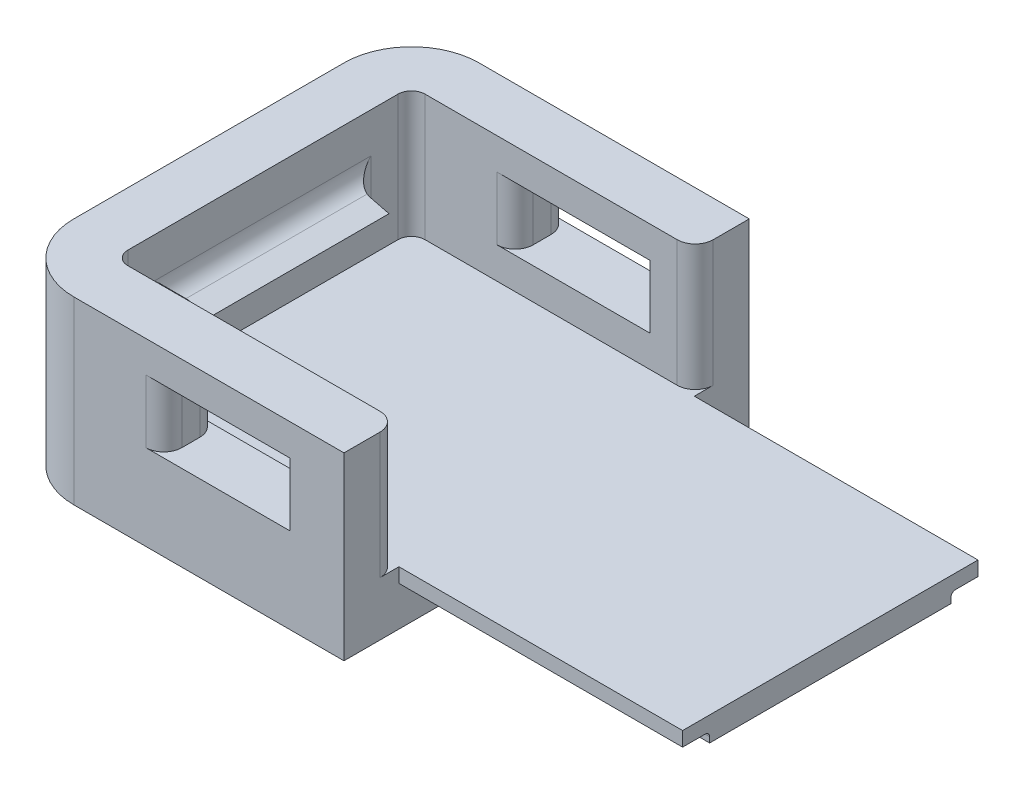
SolidWorks part; units mm, degrees
ref_plane "Alzado" through (0, 0, 0) normal (0, 0, 1) x (1, 0, 0)
ref_plane "Planta" through (0, 0, 0) normal (0, 1, 0) x (1, 0, 0)
ref_plane "Vista lateral" through (0, 0, 0) normal (1, 0, 0) x (0, 0, -1)
sketch "Croquis1" plane through (0, 0, 0) normal (0, 1, 0) x (1, 0, 0)
  line L0 (18.75, 0) -> (-18.75, 0) construction
  line L1 (15, 11.25) -> (-15, 11.25)
  line L2 (15, -11.25) -> (-15, -11.25)
  line L3 (-18.75, 7.5) -> (-18.75, -7.5)
  line L4 (18.75, 7.5) -> (18.75, -7.5)
  line L5 (0, -11.25) -> (0, 11.25) construction
  arc A0 (18.75, -7.5) -> (15, -11.25) centre (15, -7.5) cw
  arc A1 (-15, -11.25) -> (-18.75, -7.5) centre (-15, -7.5) cw
  arc A2 (18.75, 7.5) -> (15, 11.25) centre (15, 7.5) ccw
  arc A3 (-15, 11.25) -> (-18.75, 7.5) centre (-15, 7.5) ccw
  point P3 (0, 0)
  point P18 (0, 0)
  dimension "D1" = 3.75
  dimension "D2" = 37.5
  dimension "D3" = 22.5
  dimension "D4" = 7.5
extrude "Saliente-Extruir1" add sketch "Croquis1" along normal blind 3
sketch "Croquis2" plane through (0, 0, 0) normal (0, -1, 0) x (1, 0, 0)
  line L0 (15, -11.25) -> (-15, -11.25) construction
  circle A1 centre (0, 0) radius 7.63
  point P3 (0, -11.25)
  dimension "D1" = 15.26
extrude "Saliente-Extruir2" add sketch "Croquis2" along normal blind 3
sketch "Croquis3" plane through (0, 0, 0) normal (0, 0, 1) x (1, 0, 0)
  line L0 (7.63, -1.0671) -> (7.63, -3)
  line L1 (7.73, -1) -> (7.73, -3) construction
  line L2 (7.63, -1.0671) -> (9.73, -1.9262)
  line L3 (7.73, -1) -> (9.93, -1.9) construction
  line L4 (0, -3) -> (7.73, -3) construction
  line L5 (9.93, -1.9) -> (9.93, -3) construction
  line L6 (9.93, -3) -> (7.73, -3) construction
  line L7 (9.73, -3) -> (9.73, -1.9262) construction
  line L8 (7.73, -1.108) -> (9.73, -1.9262) construction
  line L9 (9.73, -1.9262) -> (9.73, -3)
  line L11 (7.73, -1.108) -> (7.73, -3) construction
  line L12 (-7.63, -3) -> (7.63, -3) construction
  line L13 (0, -3) -> (0, 0) construction
  line L14 (7.63, -3) -> (7.63, 0) construction
  line L15 (7.63, -3) -> (9.73, -3)
  dimension "D1" = 2.2
  dimension "D2" = 1.1
  dimension "D3" = 0.2
  dimension "D4" = 0.1
  dimension "D5" = 7.73
  dimension "D6" = 112.249
revolve "Revolución1" add sketch "Croquis3" angle 45 about L13 other way angle 15
sketch "Croquis5" plane through (0, 0, 0) normal (0, 0, 1) x (1, 0, 0)
  line L1 (-7.63, -3) -> (7.37, -3) construction
  line L3 (7.63, -1.0671) -> (7.63, -3) construction
  line L11 (7.73, -1) -> (7.73, -3) construction
  line L12 (-9.73, -1.9262) -> (-9.73, -3)
  line L13 (7.63, -1.0671) -> (9.73, -1.9262) construction
  line L18 (-7.63, -3) -> (-9.73, -3)
  line L19 (7.73, -1) -> (9.93, -1.9) construction
  line L20 (0, -3) -> (7.73, -3) construction
  line L25 (9.93, -1.9) -> (9.93, -3) construction
  line L26 (9.93, -3) -> (7.73, -3) construction
  line L27 (9.73, -3) -> (9.73, -1.9262) construction
  line L28 (7.73, -1.108) -> (9.73, -1.9262) construction
  line L29 (9.73, -1.9262) -> (9.73, -3) construction
  line L30 (7.73, -1.108) -> (7.73, -3) construction
  line L31 (0, -3) -> (0, 0) construction
  line L32 (7.63, -3) -> (9.73, -3) construction
  line L33 (-7.63, -1.0671) -> (-7.63, -3)
  line L34 (-7.63, -1.0671) -> (-9.73, -1.9262)
  dimension "D1" = 2.2
  dimension "D2" = 1.1
  dimension "D3" = 0.2
  dimension "D4" = 112.249
  dimension "D5" = 7.73
  dimension "D6" = 0.1
  dimension "D7" = 1.9329
revolve "Revolución2" add sketch "Croquis5" angle 45 about L31 other way angle 15
sketch "Croquis6" plane through (0, -3, 0) normal (0, -1, 0) x (1, 0, 0)
  line L0 (0, 0) -> (9.5627, -2.5623) construction
  line L1 (0, 0) -> (-9.5627, 2.5623) construction
  circle A2 centre (-9.5627, 2.5623) radius 1
  circle A3 centre (9.5627, -2.5623) radius 1
  dimension "D1" = 2
  dimension "D2" = 15
  dimension "D3" = 9.9
extrude "Cortar-Extruir1" cut sketch "Croquis6" against normal up to next
fillet "Redondeo4" radius 1 14 edges at (9.3985, -2.4631, 2.5183) (9.0986, -2.4631, -3.4481) (9.6036, -2.4631, -1.5631) (6.8801, -2.4631, -6.8801) (5.3952, -2.0336, -5.3952) (7.37, -2.0336, 1.9748) (-7.37, -2.0336, -1.9748) (-9.3985, -2.4631, -2.5183) (-9.6036, -2.4631, 1.5631) (-9.0986, -2.4631, 3.4481) (-5.3952, -2.0336, 5.3952) (-6.8801, -2.4631, 6.8801) (-7.37, -1.0671, 1.9748) (7.37, -1.0671, -1.9748)
sketch "Croquis8" plane through (0, 3, 0) normal (0, 1, 0) x (1, 0, 0)
  line L0 (15, 8.25) -> (-15, 8.25)
  line L1 (-15.75, 7.5) -> (-15.75, -7.5)
  line L2 (-15, -8.25) -> (15, -8.25)
  line L3 (15.75, -7.5) -> (15.75, 7.5)
  line L4 (18.75, -7.5) -> (18.75, 7.5)
  line L5 (15, 11.25) -> (-15, 11.25)
  line L6 (-18.75, 7.5) -> (-18.75, -7.5)
  line L7 (-15, -11.25) -> (15, -11.25)
  line L8 (18.75, -7.5) -> (18.75, 7.5)
  line L9 (15, 11.25) -> (-15, 11.25)
  line L10 (-18.75, 7.5) -> (-18.75, -7.5)
  line L11 (-15, -11.25) -> (15, -11.25)
  arc A0 (-15, 8.25) -> (-15.75, 7.5) centre (-15, 7.5) ccw
  arc A1 (-15.75, -7.5) -> (-15, -8.25) centre (-15, -7.5) ccw
  arc A2 (15, -8.25) -> (15.75, -7.5) centre (15, -7.5) ccw
  arc A3 (15.75, 7.5) -> (15, 8.25) centre (15, 7.5) ccw
  arc A4 (15, -11.25) -> (18.75, -7.5) centre (15, -7.5) ccw
  arc A5 (18.75, 7.5) -> (15, 11.25) centre (15, 7.5) ccw
  arc A6 (-15, 11.25) -> (-18.75, 7.5) centre (-15, 7.5) ccw
  arc A7 (-18.75, -7.5) -> (-15, -11.25) centre (-15, -7.5) ccw
  arc A8 (15, -11.25) -> (18.75, -7.5) centre (15, -7.5) ccw
  arc A9 (18.75, 7.5) -> (15, 11.25) centre (15, 7.5) ccw
  arc A10 (-15, 11.25) -> (-18.75, 7.5) centre (-15, 7.5) ccw
  arc A11 (-18.75, -7.5) -> (-15, -11.25) centre (-15, -7.5) ccw
  dimension "D1" = 0
  dimension "D2" = 3
extrude "Saliente-Extruir3" add sketch "Croquis8" along normal blind 7
fillet "Redondeo10" [suppressed] radius 1
sketch "Croquis11" plane through (0, 0, 0) normal (0, 0, 1) x (1, 0, 0)
  line L0 (0, 10) -> (0, 3)
  line L1 (-15, 10) -> (15, 10) construction
  line L2 (-15, 3) -> (15, 3) construction
  line L3 (0, 3) -> (15.75, 3)
  line L4 (15.75, 3) -> (15.75, 1.65)
  line L5 (15.75, 1.65) -> (0, 1.65)
  line L6 (0, 1.65) -> (0, 0)
  line L7 (0, 0) -> (-9.73, 0)
  line L8 (-15, 0) -> (15, 0) construction
  line L9 (-9.73, 0) -> (-9.73, -3)
  line L10 (-9.73, -3) -> (18.75, -3)
  line L11 (0, 10) -> (18.75, 10)
  line L12 (18.75, 10) -> (18.75, -3)
  line L13 (-9.6931, -3) -> (-9.1298, -3) construction
  point P19 (-9.6931, -3)
  point P22 (-9.73, -3)
  dimension "D1" = 1.35
extrude "Cortar-Extruir3" cut sketch "Croquis11" against normal through all both and the other way through all
sketch "Croquis12" plane through (15.75, 0, 0) normal (1, 0, 0) x (0, 0, -1)
  line L0 (0, 0) -> (0, 3) construction
  line L1 (7.5, 3) -> (-7.5, 3) construction
  line L11 (-11.25, 3) -> (-8.2, 3)
  line L12 (-11.25, 3) -> (-11.25, 1.65)
  line L13 (-11.25, 1.65) -> (-6.7, 1.65)
  line L14 (-8.2, 3) -> (-8.2, 2.2)
  line L16 (-8.2, 2.2) -> (-6.7, 2.2)
  line L19 (-6.7, 2.2) -> (-6.7, 1.65)
  line L20 (11.25, 3) -> (11.25, 1.65)
  line L21 (11.25, 3) -> (8.2, 3)
  line L22 (8.2, 3) -> (8.2, 2.2)
  line L23 (8.2, 2.2) -> (6.7, 2.2)
  line L24 (6.7, 2.2) -> (6.7, 1.65)
  line L25 (11.25, 1.65) -> (6.7, 1.65)
  point P10 (0, 0)
  point P11 (-6.7, 1.5369)
  point P12 (0, 0)
  point P19 (-6.6869, 1.6)
  point P25 (0, 0)
  point P26 (0, 0)
  dimension "D1" = 0.8
  dimension "D2" = 1.5
  dimension "D3" = 1.35
  dimension "D4" = 3.05
extrude "Cortar-Extruir4" cut sketch "Croquis12" against normal up to surface (15.75 mm away) and the other way through all up to face at (0, 6.5, 9.75)
fillet "Redondeo12" radius 0.25 2 edges at (7.875, 2.2, -6.7) (7.875, 2.2, 6.7)
sketch "Croquis13" plane through (0, 0, 11.25) normal (0, 0, 1) x (1, 0, 0)
  line L0 (0, 10) -> (0, 0) construction
  line L1 (-10, 8.25) -> (-3, 8.25)
  line L2 (-10, 8.25) -> (-10, 4.75)
  line L3 (-10, 4.75) -> (-3, 4.75)
  line L4 (-3, 8.25) -> (-3, 4.75)
  line L6 (-15, 10) -> (0, 10) construction
  point P6 (-10, 6.5)
  dimension "D1" = 3.5
  dimension "D2" = 7
  dimension "D3" = 3
  dimension "D4" = 3.5
extrude "Cortar-Extruir5" cut sketch "Croquis13" against normal up to surface (22.5 mm away) up to face at (-7.5, 5, -11.25)
fillet "Redondeo15" radius 1 4 edges at (-10, 6.5, 8.25) (-10, 6.5, -11.25) (-10, 6.5, -8.25) (-10, 6.5, 11.25)
chamfer "Chaflán1" distance 0.5 angle 45 2 edges at (-3, 6.5, 8.25) (-3, 6.5, -8.25)
sketch "Croquis14" plane through (0, 0, 0) normal (0, 0, 1) x (1, 0, 0)
  line L0 (-15.75, 6.5) -> (-13.75, 6.5) construction
  line L3 (-15.75, 10) -> (-15.75, 3) construction
  line L4 (-15.75, 7) -> (-13.75, 6.5)
  line L5 (-15.75, 6) -> (-13.75, 6.5)
  line L6 (-15.75, 7) -> (-15.75, 6)
  dimension "D1" = 2
  dimension "D2" = 1
extrude "Saliente-Extruir4" add sketch "Croquis14" against normal blind 5 and the other way blind 5
fillet "Redondeo16" radius 1 4 edges at (-15.75, 6.5, 5) (-15.75, 6.5, -5) (-15.75, 6, 0) (-15.75, 7, 0)
fillet "Redondeo18" radius 1 2 edges at (0, 6.5, 8.25) (0, 6.5, -8.25)
